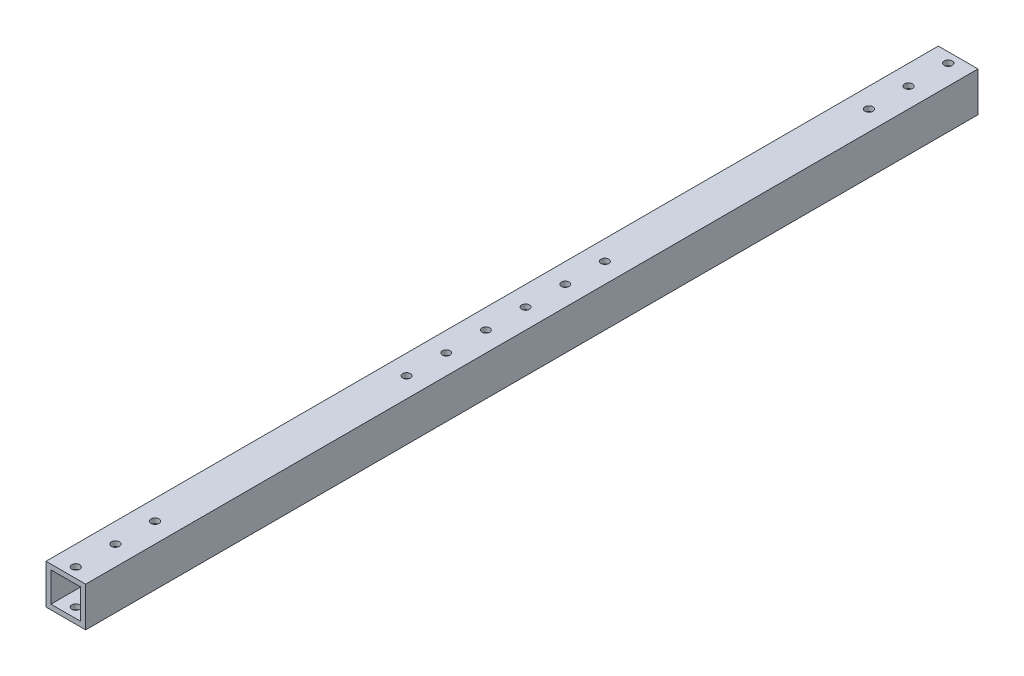
SolidWorks part; units mm, degrees
material "6061-T6 (SS)"
ref_plane "Front Plane" through (0, 0, 0) normal (0, 0, 1) x (1, 0, 0)
ref_plane "Top Plane" through (0, 0, 0) normal (0, 1, 0) x (1, 0, 0)
ref_plane "Right Plane" through (0, 0, 0) normal (1, 0, 0) x (0, 0, -1)
sketch "Sketch1" plane through (0, 0, 0) normal (0, 0, 1) x (1, 0, 0)
  line L1 (-12.7, -12.7) -> (12.7, -12.7)
  line L2 (-12.7, -12.7) -> (-12.7, 12.7)
  line L3 (-12.7, 12.7) -> (12.7, 12.7)
  line L4 (12.7, -12.7) -> (12.7, 12.7)
  line L5 (-12.7, -12.7) -> (12.7, 12.7) construction
  line L6 (-12.7, 12.7) -> (12.7, -12.7) construction
  point P0 (0, 0)
  dimension "D1" = 25.4
  dimension "D2" = 25.4
extrude "Extrude-Thin1" add sketch "Sketch1" along normal blind 571.5 thin thin type one direction reverse wall 3.175
hole_wizard "#10 Clearance Hole1" positions "3DSketch1" profile "Sketch3" hole size "#10" standard "ANSI Inch" end condition through all
sketch3d "3DSketch1"
  line L1 (12.7, 12.7, 0) -> (-12.7, 12.7, 0) construction
  line L6 (0, 12.7, 571.5) -> (0, 12.7, 0) construction
  line L7 (12.7, 12.7, 571.5) -> (-12.7, 12.7, 571.5) construction
  point P57 (0, 12.7, 6.35)
  point P59 (0, 12.7, 31.75)
  point P61 (0, 12.7, 57.15)
  point P63 (0, 12.7, 539.75)
  point P65 (0, 12.7, 514.35)
  point P67 (0, 12.7, 565.15)
  dimension "D1" = 25.4
  dimension "D2" = 25.4
  dimension "D3" = 6.35
  dimension "D4" = 25.4
  dimension "D5" = 25.4
  dimension "D6" = 6.35
sketch "Sketch3" plane through (0, 12.7, 565.15) normal (1, 0, 0) x (0, 0, 1)
  line L0 (0, 0) -> (0, 25.4)
  line L1 (0, 25.4) -> (2.5527, 25.4)
  line L2 (2.5527, 25.4) -> (2.5527, 0)
  line L5 (2.5527, 0) -> (0, 0)
  line L11 (0, -6.35) -> (0, 107.95) construction
  dimension "Thru Hole Dia." = 5.1054
  dimension "Thru Hole Depth" = 25.4
hole_wizard "3/16 (0.195) Diameter Hole2" positions "Sketch6" profile "Sketch7" hole size "3/16" standard "ANSI Inch" end condition through all
sketch "Sketch6" plane through (0, -12.7, 0) normal (0, -1, 0) x (-1, 0, 0)
  point P23 (0.0807, -226.187)
  point P26 (0.0807, -251.587)
  point P29 (0.0807, -276.987)
  point P32 (0.0807, -302.387)
  point P35 (0.0807, -327.787)
  point P38 (0.0807, -353.187)
sketch "Sketch7" plane through (-0.0807, -12.7, 226.187) normal (1, 0, 0) x (0, 0, -1)
  line L0 (0, 0) -> (0, 25.4)
  line L1 (0, 25.4) -> (2.4765, 25.4)
  line L2 (2.4765, 25.4) -> (2.4765, 0)
  line L5 (2.4765, 0) -> (0, 0)
  line L11 (0, -6.35) -> (0, 107.95) construction
  dimension "Thru Hole Dia." = 4.953
  dimension "Thru Hole Depth" = 25.4
